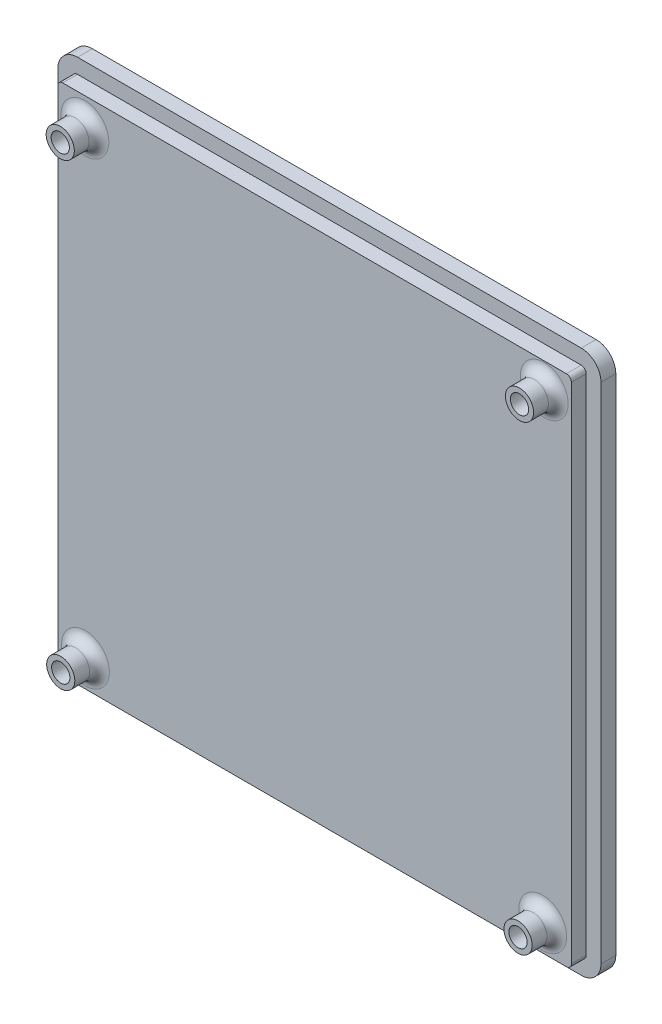
SolidWorks part; units mm, degrees
material "ABS"
ref_plane "Alzado" through (0, 0, 0) normal (0, 0, 1) x (1, 0, 0)
ref_plane "Planta" through (0, 0, 0) normal (0, 1, 0) x (1, 0, 0)
ref_plane "Vista lateral" through (0, 0, 0) normal (1, 0, 0) x (0, 0, -1)
sketch "Croquis4" plane through (0, 0, 0) normal (0, 0, 1) x (1, 0, 0)
  line L0 (-52, 52) -> (52, 52)
  line L1 (-50, 50) -> (50, 50)
  line L2 (-50, 50) -> (-50, -50)
  line L3 (-50, -50) -> (50, -50)
  line L4 (50, 50) -> (50, -50)
  line L5 (-50, 50) -> (50, -50) construction
  line L6 (-50, -50) -> (50, 50) construction
  line L7 (52, 52) -> (52, -52)
  line L8 (-52, -52) -> (52, -52)
  line L9 (-52, 52) -> (-52, -52)
  circle A0 centre (-46.5, 46.3) radius 1.85
  circle A1 centre (46.5, 46.9) radius 1.85
  circle A2 centre (-46.4, -46.6) radius 1.85
  circle A3 centre (46.2, -46.7) radius 1.85
  point P0 (0, 0)
  dimension "D3" = 3.7
  dimension "D4" = 3.7
  dimension "D5" = 3.5
  dimension "D6" = 3.5
  dimension "D7" = 3.1
  dimension "D8" = 3.4
  dimension "D9" = 3.6
  dimension "D10" = 3.8
  dimension "D11" = 3.3
  dimension "D12" = 92.6
  dimension "D1" = 100
  dimension "D2" = 100
  dimension "D13" = 2
extrude "Saliente-Extruir2" add sketch "Croquis4" along normal blind 6 contours A1 | A3 | L0 L7 L8 L9 | A0 | A2 region at (46.5, 46.9, 0) region at (46.2, -46.7, 0)
sketch "Croquis5" plane through (0, 0, 6) normal (0, 0, 1) x (1, 0, 0)
  line L4 (50, 50) -> (-50, 50)
  line L5 (50, -50) -> (50, 50)
  line L6 (-50, -50) -> (50, -50)
  line L7 (-50, 50) -> (-50, -50)
  line L8 (50, 50) -> (-50, 50)
  line L9 (50, -50) -> (50, 50)
  line L10 (-50, -50) -> (50, -50)
  line L11 (-50, 50) -> (-50, -50)
  line L12 (-52, -52) -> (52, -52)
  line L13 (-52, 52) -> (-52, -52)
  line L14 (52, 52) -> (-52, 52)
  line L15 (52, -52) -> (52, 52)
  line L16 (-52, -52) -> (52, -52)
  line L17 (-52, 52) -> (-52, -52)
  line L18 (52, 52) -> (-52, 52)
  line L19 (52, -52) -> (52, 52)
  circle A0 centre (-46.5, 46.3) radius 2.85
  circle A1 centre (46.2, -46.7) radius 1.85
  circle A2 centre (46.2, -46.7) radius 1.85
  circle A3 centre (-46.4, -46.6) radius 1.85
  circle A4 centre (-46.4, -46.6) radius 1.85
  circle A5 centre (46.5, 46.9) radius 1.85
  circle A6 centre (46.5, 46.9) radius 1.85
  circle A7 centre (-46.5, 46.3) radius 1.85
  circle A8 centre (-46.5, 46.3) radius 1.85
  circle A9 centre (46.5, 46.9) radius 2.85
  circle A10 centre (46.2, -46.7) radius 2.85
  circle A11 centre (-46.4, -46.6) radius 2.85
  circle M14 centre (46.5, 46.9) radius 1.85
  dimension "D1" = 0
  dimension "D2" = 0
  dimension "D3" = 0
  dimension "D4" = 0
  dimension "D5" = 0
  dimension "D6" = 0
  dimension "D7" = 1
extrude "Saliente-Extruir3" add sketch "Croquis5" along normal blind 5 contours M14 | A6 | A9 | A8 | A0 | A4 | A11 | A2 | A10 region at (46.5, 46.9, 6)
fillet "Redondeo1" radius 2 4 edges at (49.05, -46.7, 6) (-43.55, -46.6, 6) (-43.65, 46.3, 6) (49.35, 46.9, 6)
fillet "Redondeo2" radius 1 4 edges at (52, -52, 3) (-52, -52, 3) (-52, 52, 3) (52, 52, 3)
sketch "Croquis6" plane through (0, 0, 0) normal (0, 0, -1) x (-1, 0, 0)
  line L0 (51, 55) -> (-51, 55)
  line L1 (-55, 51) -> (-55, -51)
  line L2 (-51, -55) -> (51, -55)
  line L3 (55, -51) -> (55, 51)
  line L4 (-52, 51) -> (-52, -51)
  line L5 (-51, -52) -> (51, -52)
  line L6 (52, -51) -> (52, 51)
  line L7 (51, 52) -> (-51, 52)
  line L8 (-52, 51) -> (-52, -51)
  line L9 (-51, -52) -> (51, -52)
  line L10 (52, -51) -> (52, 51)
  line L11 (51, 52) -> (-51, 52)
  arc A0 (-51, 55) -> (-55, 51) centre (-51, 51) ccw
  arc A1 (-55, -51) -> (-51, -55) centre (-51, -51) ccw
  arc A2 (51, -55) -> (55, -51) centre (51, -51) ccw
  arc A3 (55, 51) -> (51, 55) centre (51, 51) ccw
  arc A4 (-52, -51) -> (-51, -52) centre (-51, -51) ccw
  arc A5 (51, -52) -> (52, -51) centre (51, -51) ccw
  arc A6 (52, 51) -> (51, 52) centre (51, 51) ccw
  arc A7 (-51, 52) -> (-52, 51) centre (-51, 51) ccw
  arc A8 (-52, -51) -> (-51, -52) centre (-51, -51) ccw
  arc A9 (51, -52) -> (52, -51) centre (51, -51) ccw
  arc A10 (52, 51) -> (51, 52) centre (51, 51) ccw
  arc A11 (-51, 52) -> (-52, 51) centre (-51, 51) ccw
  dimension "D3" = 4
  dimension "D1" = 0
  dimension "D2" = 3
extrude "Saliente-Extruir4" add sketch "Croquis6" against normal blind 3
